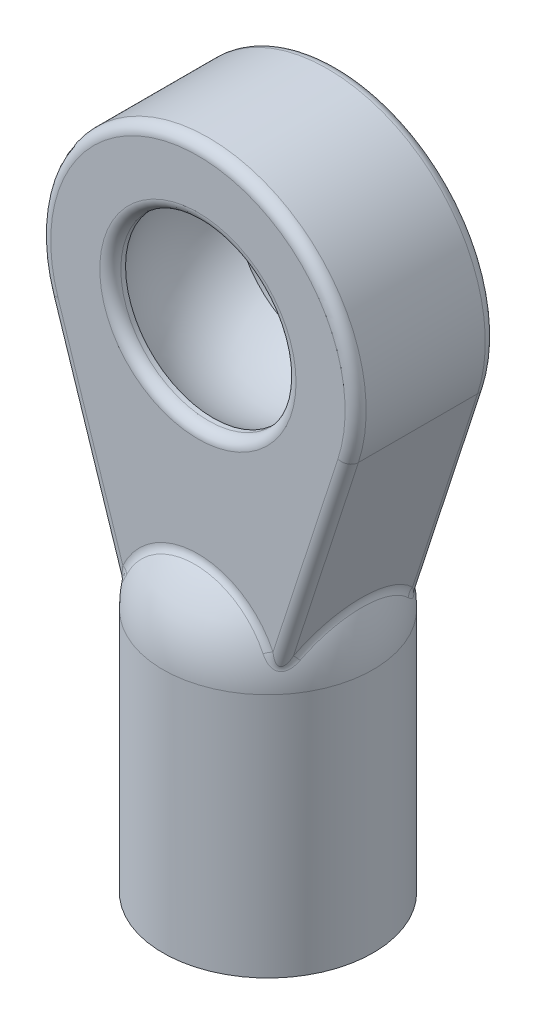
SolidWorks part; units mm, degrees
material "Acier inoxydable chromé"
ref_plane "Plan de face" through (0, 0, 0) normal (0, 0, 1) x (1, 0, 0)
ref_plane "Plan de dessus" through (0, 0, 0) normal (0, 1, 0) x (1, 0, 0)
ref_plane "Plan de droite" through (0, 0, 0) normal (1, 0, 0) x (0, 0, -1)
sketch "Esquisse1" plane through (0, 0, 0) normal (0, 0, 1) x (1, 0, 0)
  line L0 (0, 6) -> (0, 10)
  line L6 (-3, 7) -> (-3, 0)
  line L7 (-3, 0) -> (-1.5, 0)
  line L8 (-1.5, 6) -> (-1.5, 0)
  line L9 (-1.5, 6) -> (0, 6)
  line L10 (0, -0.675) -> (0, 10.4089) construction
  arc A1 (0, 10) -> (-3, 7) centre (0, 7) ccw
  dimension "D4" = 3
  dimension "D2" = 3
  dimension "D1" = 7
  dimension "D3" = 6
  dimension "D5" = 6
revolve "Révolution1" add sketch "Esquisse1" angle 360 about L10
sketch "Esquisse2" plane through (0, 0, 0) normal (0, 0, 1) x (1, 0, 0)
  line L0 (-1.5, 6) -> (1.5, 6) construction
  line L1 (-3, 0) -> (3, 0) construction
  line L2 (-2.1322, 7) -> (-4.2798, 13.6094)
  line L3 (2.1322, 7) -> (4.2798, 13.6094)
  line L4 (0, -0.5984) -> (0, 19.7324) construction
  line L6 (-2.1322, 7) -> (2.1322, 7)
  arc A3 (4.2798, 13.6094) -> (-4.2798, 13.6094) centre (0, 15) ccw
  circle A4 centre (0, 15) radius 2.5
  point P12 (0, 7)
  dimension "D1" = 18
  dimension "D2" = 4.5
  dimension "D5" = 5
  dimension "D3" = 1
  dimension "D4" = 15
extrude "Boss.-Extru.1" add sketch "Esquisse2" along normal blind 2 and the other way blind 2
sketch "Esquisse3" plane through (0, 0, 0) normal (0, 0, 1) x (1, 0, 0)
  line L0 (0, -0.5984) -> (0, 19.7324) construction
  line L1 (0, 17.95) -> (0, 12.05)
  line L2 (0, 11.0652) -> (0, 18.6849) construction
  arc A0 (0, 17.95) -> (0, 12.05) centre (0, 15) ccw
  dimension "D1" = 2.95
revolve "Enlèvement de matière-Révolution1" cut sketch "Esquisse3" angle 360 about L2
fillet "Congé1" radius 0.3 12 edges at (-2.6118, 8.476, 0) (2.6118, 8.476, 0) (0, 19.5, -2) (-3.2498, 10.4394, -2) (0, 9.2361, -2) (3.2498, 10.4394, -2) (2.5, 15, -2) (2.5, 15, 2) (-3.2498, 10.4394, 2) (0, 19.5, 2) (3.2498, 10.4394, 2) (0, 9.2361, 2)
